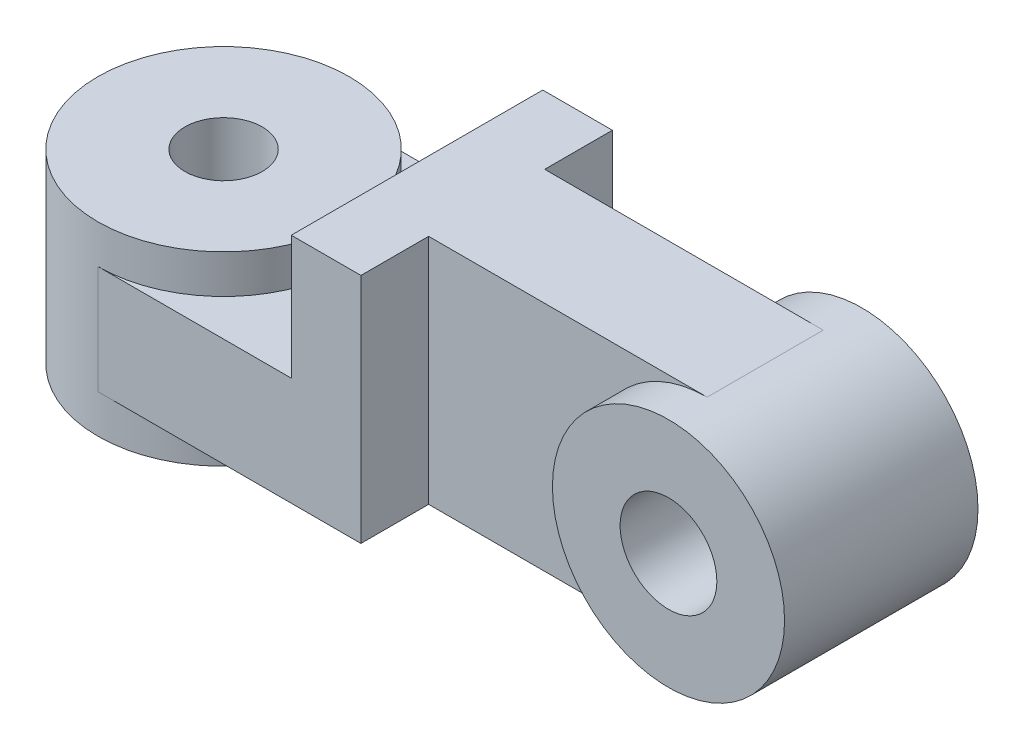
SolidWorks part; units mm, degrees
material "Alloy Steel"
ref_plane "Front Plane" through (0, 0, 0) normal (0, 0, 1) x (1, 0, 0)
ref_plane "Top Plane" through (0, 0, 0) normal (0, 1, 0) x (1, 0, 0)
ref_plane "Right Plane" through (0, 0, 0) normal (1, 0, 0) x (0, 0, -1)
sketch "Sketch1" plane through (0, 0, 0) normal (0, 1, 0) x (1, 0, 0)
  line L0 (0, -32.5) -> (50, -32.5)
  line L1 (50, 32.5) -> (0, 32.5)
  line L2 (50, 32.5) -> (50, -32.5)
  circle A0 centre (0, 0) radius 10
  circle A1 centre (0, 0) radius 32.5
  point P6 (0, 0)
  dimension "D1" = 20
  dimension "D2" = 65
  dimension "D3" = 50
extrude "Boss-Extrude1" add sketch "Sketch1" along normal mid plane 48 contours A1 A0 region at (-31.5808, 0, 0)
extrude "Boss-Extrude2" add sketch "Sketch1<3>" along normal mid plane 28 contours A1 L0 L2 L1 region at (36.6878, 0, 0)
sketch "Sketch1<3>" plane through (0, 0, 0) normal (0, 1, 0) x (1, 0, 0) same geometry as "Sketch1"
sketch "Sketch2" plane through (50, 0, 0) normal (1, 0, 0) x (0, 0, -1)
  line L0 (32.5, 14) -> (32.5, -14) construction
  line L1 (-32.5, -14) -> (32.5, -14)
  line L2 (-32.5, -14) -> (-32.5, 46)
  line L3 (-32.5, 46) -> (32.5, 46)
  line L4 (32.5, -14) -> (32.5, 46)
  dimension "D1" = 60
extrude "Boss-Extrude3" add sketch "Sketch2" along normal blind 18
sketch "Sketch4" plane through (0, 0, 0) normal (0, 0, 1) x (1, 0, 0)
  line L0 (68, 46) -> (68, -14) construction
  line L1 (68, 46) -> (140, 46)
  line L2 (68, 46) -> (68, -14)
  line L3 (68, -14) -> (140, -14)
  line L4 (140, 46) -> (140, -14) construction
  circle A0 centre (140, 16) radius 12.5
  circle A1 centre (140, 16) radius 30
  dimension "D1" = 25
  dimension "D2" = 140
extrude "Boss-Extrude4" add sketch "Sketch4" along normal mid plane 30 contours A1 L1 L2 L3 region at (92.6818, 16, 0)
extrude "Boss-Extrude5" add sketch "Sketch4<3>" along normal mid plane 50 contours A1 L4 A0 | L4 A1 A0 region at (154.2927, 16, 0) region at (125.7073, 16, 0)
sketch "Sketch4<3>" plane through (0, 0, 0) normal (0, 0, 1) x (1, 0, 0) same geometry as "Sketch4"
